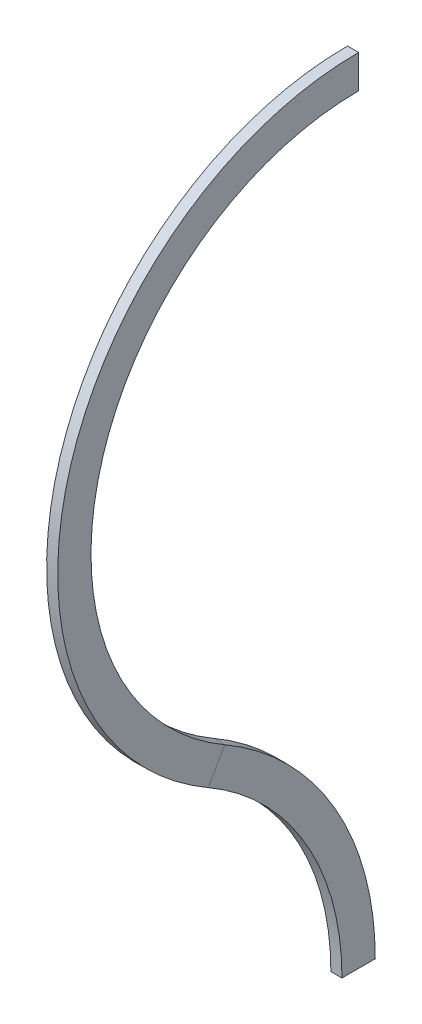
SolidWorks part; units mm, degrees
material "Thornel Mat VMA"
ref_plane "Front Plane" through (0, 0, 0) normal (0, 0, 1) x (1, 0, 0)
ref_plane "Top Plane" through (0, 0, 0) normal (0, 1, 0) x (1, 0, 0)
ref_plane "Right Plane" through (0, 0, 0) normal (1, 0, 0) x (0, 0, -1)
sketch "Sketch1" plane through (0, 0, 0) normal (1, 0, 0) x (0, 0, -1)
  line L0 (0, -35.3347) -> (0, 140) construction
  line L1 (0, 140) -> (67.935, 140) construction
  arc A0 (0, 140) -> (-25.6218, 44.3782) centre (0, 88.7564) ccw
  arc A1 (-25.6218, 44.3782) -> (0, 0) centre (-51.2436, 0) cw
  dimension "D1" = 140
sketch "Sketch2" plane through (0, 0, 0) normal (0, 1, 0) x (1, 0, 0)
  line L0 (0, 0) -> (0, 67.935) construction
  line L1 (0, 3) -> (2, 3)
  line L2 (0, 3) -> (0, -3)
  line L3 (0, -3) -> (2, -3)
  line L4 (2, 3) -> (2, -3)
  dimension "D1" = 2
  dimension "D2" = 6
  dimension "D3" = 3
sweep "Sweep1" add profiles "Sketch2" path "Sketch1"
